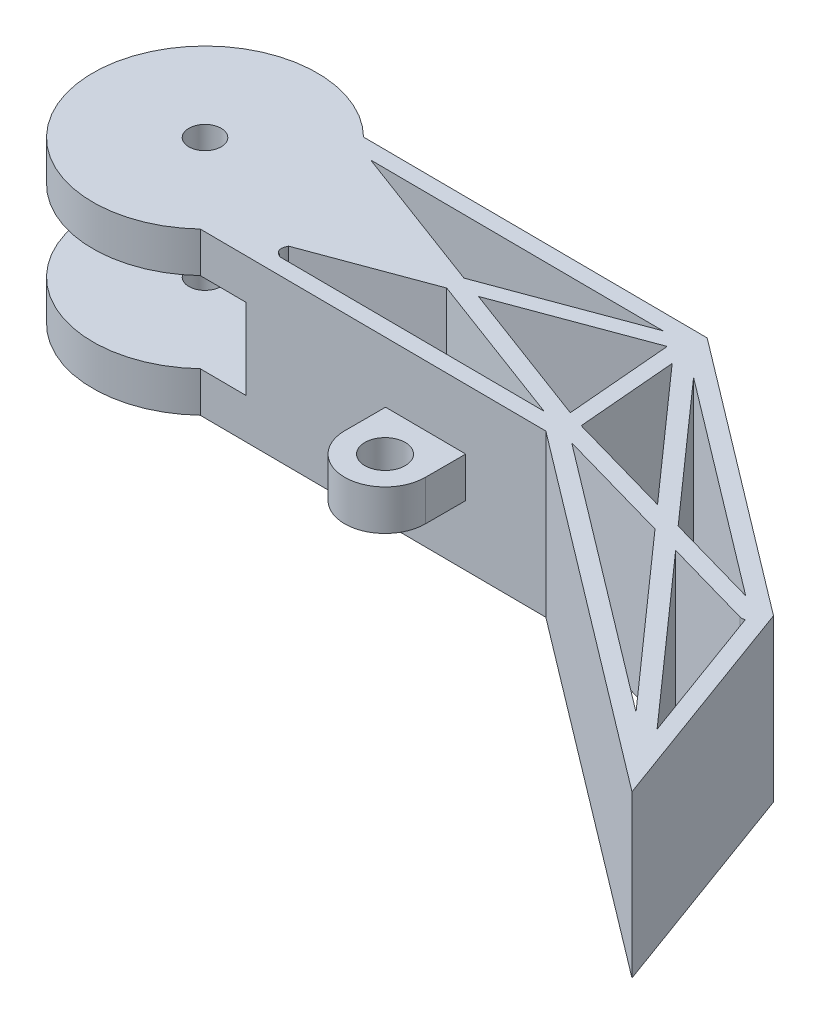
SolidWorks part; units mm, degrees
ref_plane "Front Plane" through (0, 0, 0) normal (0, 0, 1) x (1, 0, 0)
ref_plane "Top Plane" through (0, 0, 0) normal (0, 1, 0) x (1, 0, 0)
ref_plane "Right Plane" through (0, 0, 0) normal (1, 0, 0) x (0, 0, -1)
sketch "Sketch2" plane through (0, 0, 0) normal (0, 1, 0) x (1, 0, 0)
  line L0 (-86.903, -5.6011) -> (-1.9458, -5.6011) construction
  line L1 (-2.39, -19.0095) -> (53.5769, -61.4158)
  line L2 (53.5769, -61.4158) -> (40.7254, -26.2781)
  line L3 (-56.8329, 6.7281) -> (-2.3899, 6.3905)
  line L4 (40.7254, -26.2781) -> (-2.3899, 6.3905)
  line L6 (-57.1469, -18.67) -> (-2.39, -19.0095)
  arc A0 (-57.1469, -18.67) -> (-56.8329, 6.7281) centre (-69.2509, -5.8194) cw
  circle A1 centre (-69.2509, -5.8194) radius 2.54
  dimension "D3" = 25.4
extrude "Boss-Extrude4" add sketch "Sketch2" along normal blind 12.7
sketch "Sketch4" plane through (0, 12.7, 0) normal (0, 1, 0) x (1, 0, 0)
  circle A0 centre (-69.2509, -5.8194) radius 17.6534
extrude "Cut-Extrude1" cut sketch "Sketch4" against normal blind 6.35
sketch "Triangleout" plane through (0, 6.35, 0) normal (0, 1, 0) x (1, 0, 0)
  line L0 (-58.1063, -19.5103) -> (-49.4554, -19.5103)
  line L1 (-49.4554, -19.5103) -> (-53.0939, -12.9324)
  line L2 (-53.0939, -12.9324) -> (-58.1063, -19.5103)
  arc A0 (-57.1469, -18.67) -> (-56.8329, 6.7281) centre (-69.2509, -5.8194) ccw construction
  arc A1 (-56.8329, 6.7281) -> (-57.1469, -18.67) centre (-69.2509, -5.8194) ccw construction
extrude "Cut-Extrude2" cut sketch "Triangleout" along normal blind 6.35
mirror "Mirror3" about plane through (-69.2509, 12.7, 5.8194) normal (0, -1, 0) of "Cut-Extrude2", "Cut-Extrude1", "Boss-Extrude4"
sketch "Sketch5" plane through (0, 25.4, 0) normal (0, 1, 0) x (1, 0, 0)
  line L0 (-1.5294, -16.4748) -> (-3.2505, 3.8558) construction
  line L1 (48.2231, -54.1724) -> (-3.2505, 3.8558)
  line L2 (47.1512, -43.847) -> (-2.39, -6.3095) construction
  line L3 (-57.1312, -16.1301) -> (-3.2505, 3.8558)
  line L4 (53.5769, -61.4158) -> (40.7254, -26.2781) construction
  line L5 (-56.9899, -5.971) -> (-2.39, -6.3095) construction
  line L6 (-57.1469, -18.67) -> (-56.8329, 6.7281) construction
  line L7 (-56.8486, 4.1881) -> (-1.5294, -16.4748)
  line L8 (-1.5294, -16.4748) -> (38.5964, -27.8518)
  line L10 (-56.6895, -17.3208) -> (-3.6238, 2.3628)
  line L11 (47.273, -55.0152) -> (-3.6238, 2.3628)
  line L12 (-57.293, 2.9984) -> (-1.9254, -17.6825)
  line L13 (-1.9254, -17.6825) -> (38.25, -29.0736)
  line L14 (-57.5729, -14.9393) -> (-2.8772, 5.3488)
  line L15 (49.1732, -53.3296) -> (-2.8772, 5.3488)
  line L16 (-56.4043, 5.3778) -> (-1.1333, -15.267)
  line L17 (-1.1333, -15.267) -> (38.9428, -26.6299)
  line L18 (-1.5294, -16.4748) -> (-3.2505, 3.8558)
  line L19 (-0.2639, -16.3676) -> (-1.9851, 3.963)
  line L20 (-2.7949, -16.5819) -> (-4.516, 3.7487)
  line L28 (-3.2505, 3.8558) -> (-56.8486, 4.1881)
  line L29 (38.5964, -27.8518) -> (-3.2505, 3.8558)
  line L30 (48.2231, -54.1724) -> (38.5964, -27.8518)
  line L31 (-1.5294, -16.4748) -> (48.2231, -54.1724)
  line L32 (-57.1312, -16.1301) -> (-1.5294, -16.4748)
  line L33 (-3.2505, 3.8558) -> (-56.8486, 4.1881)
  line L34 (38.5964, -27.8518) -> (-3.2505, 3.8558)
  line L35 (48.2231, -54.1724) -> (38.5964, -27.8518)
  line L36 (-1.5294, -16.4748) -> (48.2231, -54.1724)
  line L37 (-57.1312, -16.1301) -> (-1.5294, -16.4748)
  arc A0 (-56.6895, -17.3208) -> (-57.5729, -14.9393) centre (-57.1312, -16.1301) cw
  arc A1 (47.273, -55.0152) -> (49.1732, -53.3296) centre (48.2231, -54.1724) ccw
  arc A2 (-57.293, 2.9984) -> (-56.4043, 5.3778) centre (-56.8486, 4.1881) cw
  arc A3 (38.25, -29.0736) -> (38.9428, -26.6299) centre (38.5964, -27.8518) ccw
  arc A4 (-0.2639, -16.3676) -> (-2.7949, -16.5819) centre (-1.5294, -16.4748) cw
  arc A5 (-1.9851, 3.963) -> (-4.516, 3.7487) centre (-3.2505, 3.8558) ccw
  arc A7 (-57.1469, -18.67) -> (-56.8329, 6.7281) centre (-69.6889, -5.814) ccw
  spline S0 degree 1 poles (-57.1312, -16.1301) (-56.8486, 4.1881) knots 0 0 1 1
  spline S1 degree 2 poles (-47.0825, -16.1924) (-48.6344, -15.5095) (-47.8598, -14.0456) knots 0 0 0 1 1 1
  dimension "D1" = 2.54
  dimension "D2" = 1.27
  dimension "D3" = 1.27
  dimension "D4" = 1.27
  dimension "D5" = 1.27
extrude "Cut-Extrude5" cut sketch "Sketch5" against normal through all contours L10 L37 L12 | L14 L33 L16 | L16 L20 L10 | A3 L13 L15 L35 | L13 L36 L11 | L17 L34 L15 | L19 L17 L11 region at (36.756, 25.4, 35.0972) region at (21.2871, 25.4, 30.8694) region at (4.8107, 25.4, 11.8628) region at (19.5694, 25.4, 15.7811) region at (-28.9114, 25.4, 13.242) region at (-11.1317, 25.4, 6.1523) region at (-29.8984, 25.4, -1.1482)
sketch3d "3DSketch1"
  point P0 (-32.4826, 11.0258, -6.5771)
sketch3d "3DSketch2"
  point P0 (-24.5315, 25.4, -6.5278)
sketch3d "3DSketch3"
  point P0 (-56.1684, 15.0984, -6.7239)
ref_plane "Plane3" through (-11.7184, 0, 0) normal (-1, 0, 0) x (0, 0, 1)
sketch "Sketch9" plane through (-11.7184, 0, 0) normal (-1, 0, 0) x (0, 0, 1)
  line L0 (-9.2681, 15.875) -> (-7.4382, 16.1357) construction
  line L2 (-6.7281, 19.05) -> (-6.7281, 6.35) construction
  line L3 (-6.7281, 18.415) -> (-6.7281, 6.985)
  line L4 (-9.2681, 9.525) -> (-7.2874, 9.2397) construction
  line L5 (-7.2874, 9.2397) -> (-6.7281, 6.985) construction
  line L6 (-7.4382, 16.1357) -> (-6.7281, 18.415) construction
  arc A0 (-9.2681, 15.875) -> (-9.2681, 9.525) centre (-9.2681, 12.7) ccw
  circle A1 centre (-9.2681, 12.7) radius 1.5875
  spline S0 degree 2 poles (-9.2681, 9.525) (-7.2874, 9.2397) (-6.7281, 6.985) knots 0 0 0 1 1 1
  spline S1 degree 2 poles (-9.2681, 15.875) (-7.4382, 16.1357) (-6.7281, 18.415) knots 0 0 0 1 1 1
  point P0 (-6.7281, 12.7)
  point P2 (-6.7382, 9.538)
  point P7 (-6.6734, 9.3457)
  point P10 (-6.7281, 6.9897)
  point P11 (0, 0)
  point P13 (-6.7027, 9.4798)
  point P14 (-6.7281, 18.5288)
  point P17 (-9.114, 15.875)
  point P18 (-6.7281, 15.875)
  point P19 (0, 0)
  point P20 (0, 0)
  point P21 (-6.7281, 18.3832)
  point P22 (-6.7397, 9.5365)
  point P23 (-7.2874, 9.2397)
  point P24 (-7.4382, 16.1357)
  dimension "D2" = 3.175
  dimension "D3" = 3.175
  dimension "D4" = 2.54
  dimension "D5" = 2.54
extrude "Boss-Extrude6" add sketch "Sketch9" along normal blind 3.175 and the other way blind 3.175 separate body
sketch3d "3DSketch4"
  point P0 (0, 0, 0)
ref_plane "Plane4" through (0, 12.7, 0) normal (0, -1, 0) x (1, 0, 0)
sketch "Sketch10" plane through (0, 12.7, 0) normal (0, -1, 0) x (1, 0, 0)
  line L0 (-27.79, 18.852) -> (-15.09, 18.9307)
  line L1 (-57.1469, 18.67) -> (-2.39, 19.0095) construction
  line L2 (-15.09, 18.9307) -> (-15.09, 25.2807)
  line L3 (-27.79, 25.2807) -> (-27.79, 18.852)
  arc A0 (-27.79, 25.2807) -> (-15.09, 25.2807) centre (-21.44, 25.2807) cw
  circle A1 centre (-21.44, 25.2807) radius 3.175
  dimension "D1" = 6.35
  dimension "D2" = 6.35
  dimension "D3" = 6.35
  dimension "D4" = 19.05
extrude "Boss-Extrude7" add sketch "Sketch10" along normal blind 3.175 and the other way blind 3.175
